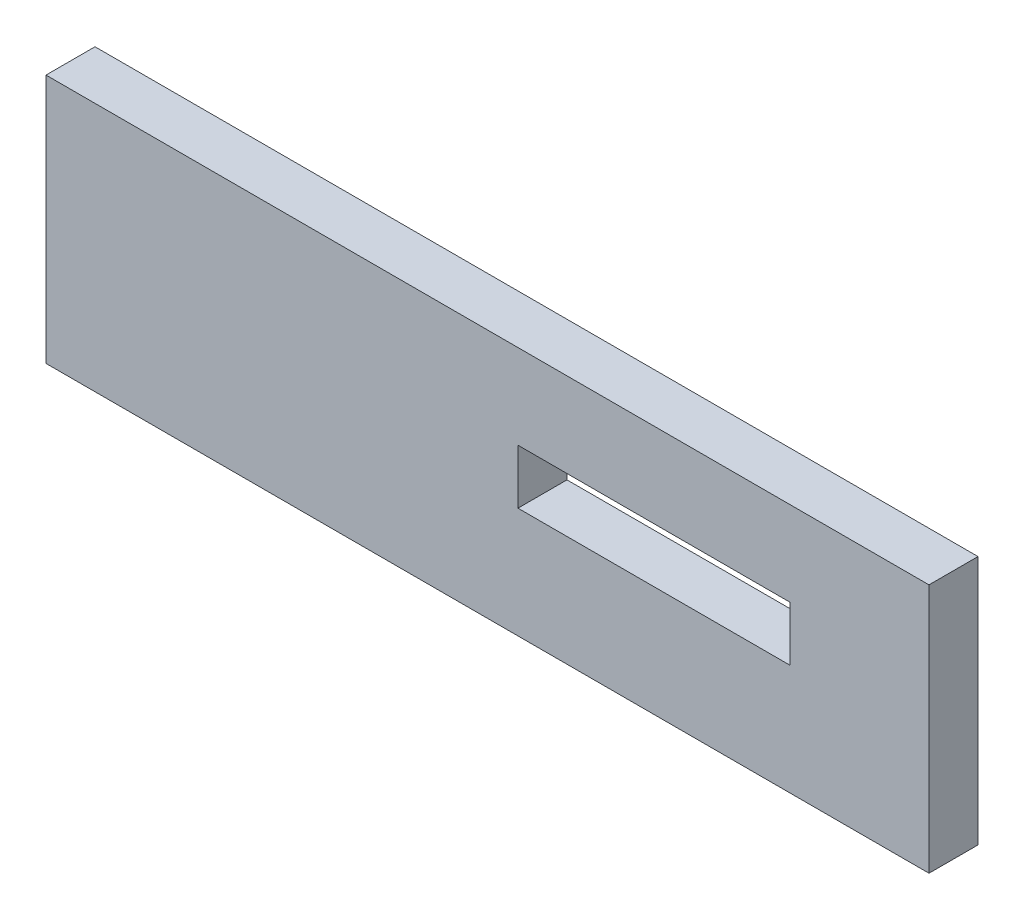
SolidWorks part; units mm, degrees
material "Custom Plastic"
ref_plane "Front Plane" through (0, 0, 0) normal (0, 0, 1) x (1, 0, 0)
ref_plane "Top Plane" through (0, 0, 0) normal (0, 1, 0) x (1, 0, 0)
ref_plane "Right Plane" through (0, 0, 0) normal (1, 0, 0) x (0, 0, -1)
sketch "Sketch1" plane through (0, 0, 0) normal (0, 0, 1) x (1, 0, 0)
  line L0 (-159.2419, -2.55) -> (-174.4419, -2.55) construction
  line L1 (-205.4985, -12) -> (-149.2419, -12)
  line L2 (-205.4985, -12) -> (-205.4985, 4)
  line L3 (-205.4985, 4) -> (-149.2419, 4)
  line L4 (-149.2419, -12) -> (-149.2419, 4)
  line L5 (-175.4419, -1.45) -> (-158.2419, -1.45)
  line L6 (-175.4419, -1.45) -> (-175.4419, -4.9)
  line L7 (-175.4419, -4.9) -> (-158.2419, -4.9)
  line L8 (-158.2419, -1.45) -> (-158.2419, -4.9)
  line L9 (-159.2419, -3.8) -> (-174.4419, -3.8) construction
  line L10 (-174.4419, -3.8) -> (-174.4419, -2.55) construction
  line L11 (-159.2419, -3.8) -> (-159.2419, -2.55) construction
  line L12 (-183.4985, -2.4493) -> (-189.9985, -2.4493) construction
  line L13 (-194.7485, 0.4507) -> (-178.7485, 0.4507)
  line L14 (-194.7485, 0.4507) -> (-194.7485, -6.0493)
  line L15 (-194.7485, -6.0493) -> (-178.7485, -6.0493)
  line L16 (-178.7485, 0.4507) -> (-178.7485, -6.0493)
  circle A0 centre (-201.1374, -5) radius 3.1
  circle A1 centre (-153.2419, -5) radius 3.1
  circle A2 centre (-153.2419, -5) radius 3.1 construction
  circle A3 centre (-201.1374, -5) radius 3.1 construction
  point P34 (-186.7485, -2.4493)
  point P35 (-186.7485, 0.4507)
  point P36 (-194.7485, -2.7993)
  dimension "D1" = 1.1
  dimension "D2" = 1.1
  dimension "D3" = 1
  dimension "D4" = 1
  dimension "D5" = 6.5
  dimension "D6" = 16
extrude "Boss-Extrude1" add sketch "Sketch1" along normal up to surface (3.101 mm away) contours A0 | A1 | L1 L4 L3 L2 A1 A0 L5 L8 L7 L6 L13 L16 L15 L14 | L16 L13 L14 L15 region at (-176.868, -4.1677, 0) region at (-186.7485, -2.7993, 0) region at (-201.1374, -5, 0) region at (-153.2419, -5, 0)
extrude "Cut-Extrude1" cut sketch "Sketch1<3>" along normal blind 3.05 from surface contours A0 | A1 region at (-201.1374, -5, 0) region at (-153.2419, -5, 0) starting at face at (-177.3702, -4, 0)
sketch "Sketch1<3>" plane through (0, 0, 0) normal (0, 0, 1) x (1, 0, 0) same geometry as "Sketch1"
extrude "Cut-Extrude2" cut sketch "Sketch1<4>" along normal blind 2.5 contours L16 L13 L14 L15 region at (-186.7485, -2.7993, 0)
sketch "Sketch1<4>" plane through (0, 0, 0) normal (0, 0, 1) x (1, 0, 0) same geometry as "Sketch1"
sketch "Sketch2" plane through (0, 0, 3.101) normal (0, 0, 1) x (1, 0, 0)
  line L0 (-205.4985, 4) -> (-149.2419, 4) construction
  line L1 (-205.2985, 3.9) -> (-149.4419, 3.9)
  line L2 (-205.2985, 3.9) -> (-205.2985, -11.9)
  line L3 (-205.2985, -11.9) -> (-149.4419, -11.9)
  line L4 (-149.4419, 3.9) -> (-149.4419, -11.9)
  line L5 (-149.2419, -12) -> (-149.2419, 4) construction
  line L7 (-205.4985, 4) -> (-149.2419, 4)
  line L8 (-205.4985, 4) -> (-205.4985, -12)
  line L9 (-205.4985, -12) -> (-149.2419, -12)
  line L10 (-149.2419, 4) -> (-149.2419, -12)
  point P6 (-177.3702, 4)
  point P7 (-177.3702, 3.9)
  point P10 (-149.2419, -4)
  point P11 (-149.4419, -4)
  dimension "D1" = 0.1
  dimension "D2" = 0.2
extrude "Cut-Extrude3" cut sketch "Sketch2" against normal up to surface (3.101 mm away) up to face at (-186.7485, -2.7993, 0)
